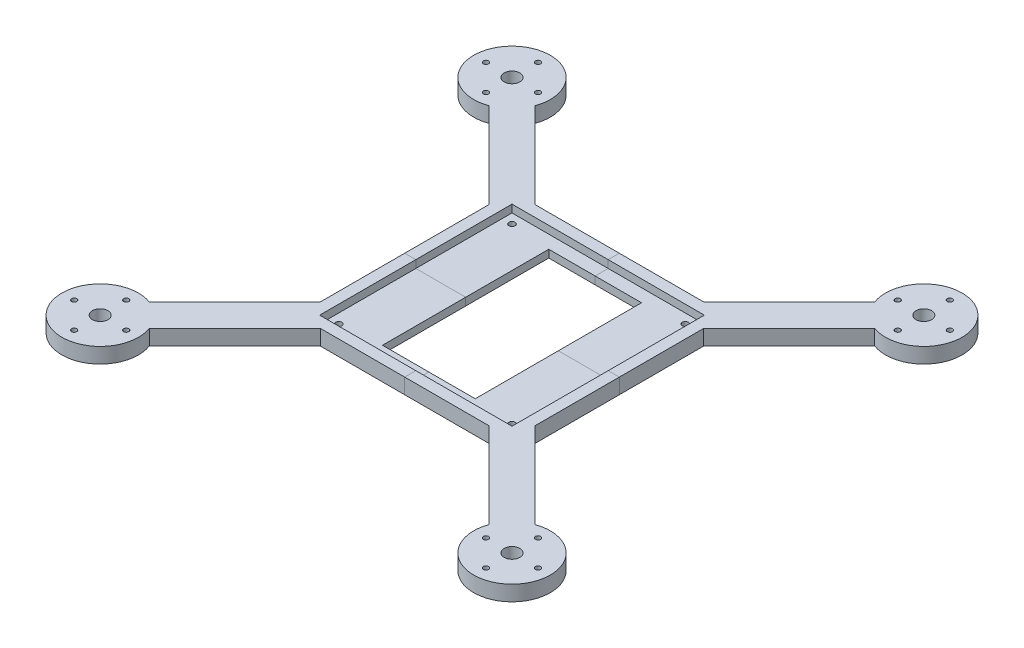
SolidWorks part; units mm, degrees
note: '?' marks a value the reader was unsure of.
ref_plane "정면" through (0, 0, 0) normal (0, 0, 1) x (1, 0, 0)
ref_plane "윗면" through (0, 0, 0) normal (0, 1, 0) x (1, 0, 0)
ref_plane "우측면" through (0, 0, 0) normal (1, 0, 0) x (0, 0, -1)
sketch "스케치1" plane through (0, 0, 0) normal (0, 1, 0) x (1, 0, 0)
  line L0 (55, 70) -> (110.8425, 125.8425)
  line L1 (-55, 70) -> (55, 70)
  line L2 (-70, 55) -> (-70, -55)
  line L3 (-55, -70) -> (55, -70)
  line L4 (70, 55) -> (70, -55)
  line L5 (-60.2755, 60.2755) -> (60.2245, -60.2245) construction
  line L6 (-77.3477, -77.3477) -> (43.1523, 43.1523) construction
  line L7 (-30.25, 54.25) -> (30.25, 54.25)
  line L8 (-30.25, 54.25) -> (-30.25, -54.25)
  line L9 (-30.25, -54.25) -> (30.25, -54.25)
  line L10 (30.25, 54.25) -> (30.25, -54.25)
  line L11 (-30.25, 54.25) -> (30.25, -54.25) construction
  line L12 (-30.25, -54.25) -> (30.25, 54.25) construction
  line L13 (70, 55) -> (125.8425, 110.8425)
  line L14 (109.3503, 134.3503) -> (159.3503, 134.3503) construction
  line L15 (134.3503, 159.3503) -> (134.3503, 109.3503) construction
  line L16 (152.028, 116.6726) -> (116.6726, 152.028) construction
  line L17 (70, -55) -> (125.8425, -110.8425)
  line L18 (55, -70) -> (110.8425, -125.8425)
  line L19 (134.3503, -109.3503) -> (134.3503, -159.3503) construction
  line L20 (159.3503, -134.3503) -> (109.3503, -134.3503) construction
  line L21 (116.6726, -152.028) -> (152.028, -116.6726) construction
  line L22 (-55, -70) -> (-110.8425, -125.8425)
  line L23 (-70, -55) -> (-125.8425, -110.8425)
  line L24 (-109.3503, -134.3503) -> (-159.3503, -134.3503) construction
  line L25 (-134.3503, -159.3503) -> (-134.3503, -109.3503) construction
  line L26 (-152.028, -116.6726) -> (-116.6726, -152.028) construction
  line L27 (-70, 55) -> (-125.8425, 110.8425)
  line L28 (-55, 70) -> (-110.8425, 125.8425)
  line L29 (-134.3503, 109.3503) -> (-134.3503, 159.3503) construction
  line L30 (-159.3503, 134.3503) -> (-109.3503, 134.3503) construction
  line L31 (-116.6726, 152.028) -> (-152.028, 116.6726) construction
  line L32 (55, 70) -> (70, 70) construction
  line L33 (70, 70) -> (70, 55) construction
  line L34 (55, -70) -> (70, -70) construction
  line L35 (70, -55) -> (70, -70) construction
  line L36 (-70, -70) -> (-55, -70) construction
  line L37 (-70, -55) -> (-70, -70) construction
  line L38 (-70, 70) -> (-70, 55) construction
  line L39 (-70, 70) -> (-55, 70) construction
  line L45 (-56.5, 56.5) -> (56.5, -56.5) construction
  line L46 (-56.5, -56.5) -> (56.5, 56.5) construction
  circle A0 centre (-56.5, -56.5) radius 2
  circle A1 centre (56.5, -56.5) radius 2
  circle A2 centre (56.5, 56.5) radius 2
  circle A3 centre (-56.5, 56.5) radius 2
  arc A4 (125.8425, 110.8425) -> (110.8425, 125.8425) centre (134.3503, 134.3503) ccw
  arc A5 (110.8425, 125.8425) -> (116.6726, 116.6726) centre (134.3503, 134.3503) ccw construction
  arc A6 (116.6726, 116.6726) -> (125.8425, 110.8425) centre (134.3503, 134.3503) ccw construction
  circle A11 centre (134.3503, 117.3503) radius 1.7
  circle A12 centre (117.3503, 134.3503) radius 1.7
  circle A13 centre (151.3503, 134.3503) radius 1.7
  circle A14 centre (134.3503, 151.3503) radius 1.7
  circle A15 centre (134.3503, 134.3503) radius 5.1
  arc A16 (110.8425, -125.8425) -> (125.8425, -110.8425) centre (134.3503, -134.3503) ccw
  circle A17 centre (117.3503, -134.3503) radius 1.7
  circle A18 centre (134.3503, -117.3503) radius 1.7
  circle A19 centre (134.3503, -151.3503) radius 1.7
  circle A20 centre (151.3503, -134.3503) radius 1.7
  circle A21 centre (134.3503, -134.3503) radius 5.1
  arc A22 (125.8425, -110.8425) -> (116.6726, -116.6726) centre (134.3503, -134.3503) ccw construction
  arc A23 (116.6726, -116.6726) -> (110.8425, -125.8425) centre (134.3503, -134.3503) ccw construction
  arc A24 (-125.8425, -110.8425) -> (-110.8425, -125.8425) centre (-134.3503, -134.3503) ccw
  circle A25 centre (-134.3503, -117.3503) radius 1.7
  circle A26 centre (-117.3503, -134.3503) radius 1.7
  circle A27 centre (-151.3503, -134.3503) radius 1.7
  circle A28 centre (-134.3503, -151.3503) radius 1.7
  circle A29 centre (-134.3503, -134.3503) radius 5.1
  arc A30 (-110.8425, -125.8425) -> (-116.6726, -116.6726) centre (-134.3503, -134.3503) ccw construction
  arc A31 (-116.6726, -116.6726) -> (-125.8425, -110.8425) centre (-134.3503, -134.3503) ccw construction
  arc A32 (-110.8425, 125.8425) -> (-125.8425, 110.8425) centre (-134.3503, 134.3503) ccw
  circle A33 centre (-117.3503, 134.3503) radius 1.7
  circle A34 centre (-134.3503, 117.3503) radius 1.7
  circle A35 centre (-134.3503, 151.3503) radius 1.7
  circle A36 centre (-151.3503, 134.3503) radius 1.7
  circle A37 centre (-134.3503, 134.3503) radius 5.1
  arc A38 (-125.8425, 110.8425) -> (-116.6726, 116.6726) centre (-134.3503, 134.3503) ccw construction
  arc A39 (-116.6726, 116.6726) -> (-110.8425, 125.8425) centre (-134.3503, 134.3503) ccw construction
  point P0 (0, 0)
  point P6 (0, 0)
  point P28 (0, 54.25)
  point P32 (134.3503, 134.3503)
  point P38 (134.3503, 134.3503)
  point P48 (0, 0)
  point P57 (134.3503, -134.3503)
  point P63 (134.3503, -134.3503)
  point P80 (-134.3503, -134.3503)
  point P86 (-134.3503, -134.3503)
  point P103 (-134.3503, 134.3503)
  point P109 (-134.3503, 134.3503)
  dimension "D5" = 4
  dimension "D13" = 50
  dimension "D14" = 3.4
  dimension "D15" = 17
  dimension "D16" = 34
  dimension "D19" = 10.2
  dimension "D1" = 140
  dimension "D2" = 140
  dimension "D3" = 108.5
  dimension "D4" = 60.5
  dimension "D6" = 56.5
  dimension "D10" = 15
  dimension "D11" = 15
  dimension "D12" = 190
  dimension "D17" = 17
  dimension "D18" = 34
  dimension "D20" = 4
extrude "보스-돌출1" add sketch "스케치1" against normal blind 10
sketch "스케치4" plane through (0, 0, 0) normal (0, 1, 0) x (1, 0, 0)
  line L1 (-62.75, 62.75) -> (62.75, 62.75)
  line L2 (-62.75, 62.75) -> (-62.75, -62.75)
  line L3 (-62.75, -62.75) -> (62.75, -62.75)
  line L4 (62.75, 62.75) -> (62.75, -62.75)
  line L5 (-62.75, 62.75) -> (62.75, -62.75) construction
  line L6 (-62.75, -62.75) -> (62.75, 62.75) construction
  point P0 (0, 0)
  dimension "D1" = 125.5
  dimension "D2" = 125.5
extrude "컷-돌출1" cut sketch "스케치4" against normal blind 5
sketch "스케치5" plane through (0, 0, 0) normal (0, 1, 0) x (1, 0, 0)
  line L0 (0, 70) -> (0, -70)
  line L1 (-70, 0) -> (70, 0)
  line L2 (-55, -70) -> (55, -70) construction
  line L3 (70, -55) -> (70, 55) construction
  point P4 (0, 0)
  point P8 (0, 0)
sketch "스케치3" plane through (0, 0, 0) normal (0, 1, 0) x (1, 0, 0)
  line L0 (0, 0) -> (134.3503, 134.3503) construction
  line L1 (134.3503, 134.3503) -> (117.4358, 128.1939)
  line L2 (128.1939, 117.4358) -> (134.3503, 134.3503)
  circle A0 centre (134.3503, 134.3503) radius 13.9
  circle A1 centre (134.3503, 134.3503) radius 18
  arc A2 (117.4358, 128.1939) -> (128.1939, 117.4358) centre (134.3503, 134.3503) ccw
  arc M49 (125.8425, 110.8425) -> (110.8425, 125.8425) centre (134.3503, 134.3503) ccw
  dimension "D1" = 27.8
  dimension "D2" = 25
  dimension "D4" = 36
  dimension "D3" = 25
extrude "보스-돌출2" [suppressed] add sketch "스케치3" along normal blind 25 contours A1 L1 A0 L2 M49
ref_axis "기준축1" through (0, 26.25, 0) along (0, -1, 0)?
pattern_circular "원형 패턴1" [suppressed] count 4 over 360 about axis through (0, 26.25, 0) along (0, -1, 0)
split "분할2" trim tools "스케치5" bodies to split 104 resulting bodies 109 110 111 112
split "분할1" bodies to split 104 resulting bodies 107
